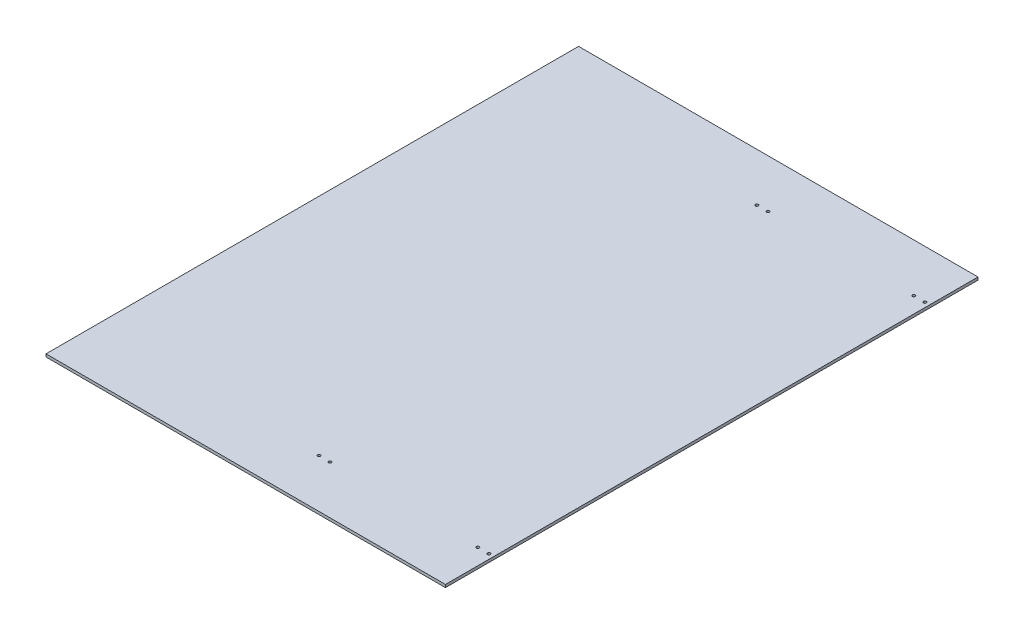
SolidWorks part; units mm, degrees
ref_plane "Front Plane" through (0, 0, 0) normal (0, 0, 1) x (1, 0, 0)
ref_plane "Top Plane" through (0, 0, 0) normal (0, 1, 0) x (1, 0, 0)
ref_plane "Right Plane" through (0, 0, 0) normal (1, 0, 0) x (0, 0, -1)
sketch "Sketch1" plane through (0, 0, 0) normal (0, 1, 0) x (1, 0, 0)
  line L1 (-457.2, -609.6) -> (457.2, -609.6)
  line L2 (-457.2, -609.6) -> (-457.2, 609.6)
  line L3 (-457.2, 609.6) -> (457.2, 609.6)
  line L4 (457.2, -609.6) -> (457.2, 609.6)
  line L5 (-457.2, -609.6) -> (457.2, 609.6) construction
  line L6 (-457.2, 609.6) -> (457.2, -609.6) construction
  point P0 (0, 0)
  dimension "D1" = 1219.2
  dimension "D2" = 914.4
extrude "Boss-Extrude1" add sketch "Sketch1" along normal blind 6.35
sketch "Sketch2" plane through (0, 0, 0) normal (0, -1, 0) x (1, 0, 0)
  line L0 (457.2, 609.6) -> (457.2, -609.6) construction
  circle A4 centre (56.9595, 498.8814) radius 3.2639
  circle A5 centre (82.3595, 498.8814) radius 3.2639
  circle A6 centre (446.0875, 498.8814) radius 3.2639
  circle A7 centre (420.6875, 498.8814) radius 3.2639
  circle A12 centre (61.722, -498.8814) radius 3.2639
  circle A13 centre (87.122, -498.8814) radius 3.2639
  circle A14 centre (420.878, -498.8814) radius 3.2639
  circle A15 centre (446.278, -498.8814) radius 3.2639
  dimension "D1" = 6.5278
  dimension "D2" = 10.922
  dimension "D3" = 11.1125
  dimension "D4" = 36.322
  dimension "D5" = 36.5125
  dimension "D6" = 370.078
  dimension "D7" = 374.8405
  dimension "D8" = 395.478
  dimension "D9" = 400.2405
  dimension "D10" = 110.7186
  dimension "D11" = 1108.4814
extrude "Cut-Extrude1" cut sketch "Sketch2" against normal through all
